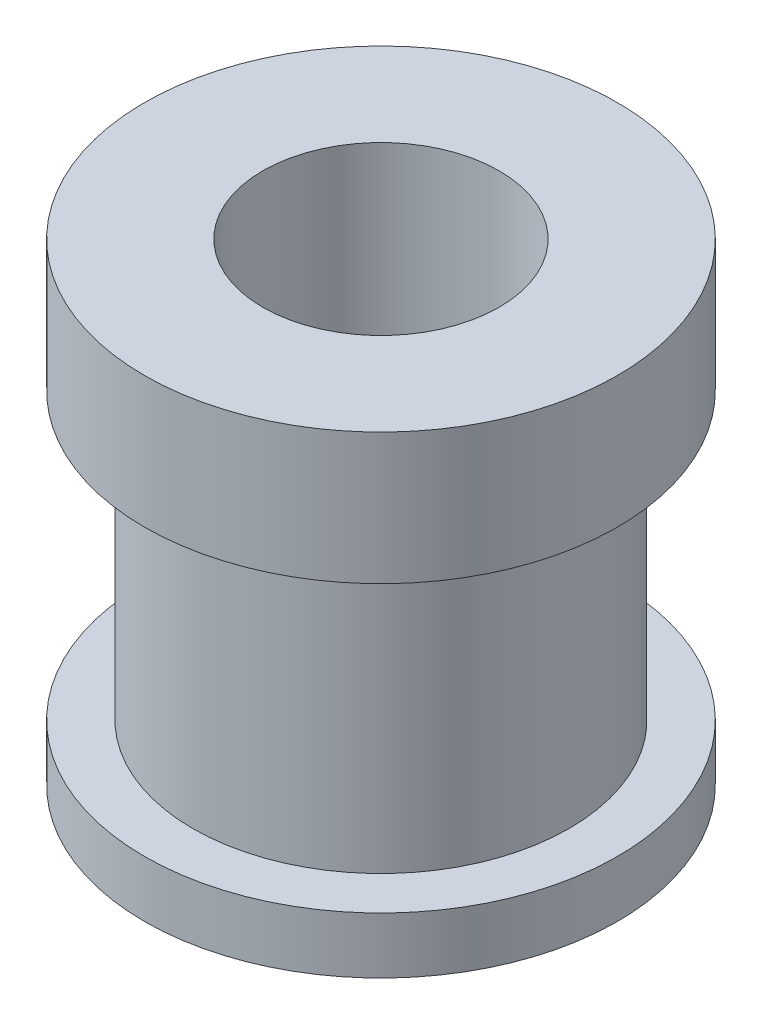
SolidWorks part; units mm, degrees
material "6063-T6"
ref_plane "Front Plane" through (0, 0, 0) normal (0, 0, 1) x (1, 0, 0)
ref_plane "Top Plane" through (0, 0, 0) normal (0, 1, 0) x (1, 0, 0)
ref_plane "Right Plane" through (0, 0, 0) normal (1, 0, 0) x (0, 0, -1)
sketch "Sketch1" plane through (0, 0, 0) normal (0, 1, 0) x (1, 0, 0)
  circle A0 centre (0, 0) radius 8
  dimension "D1" = 16
extrude "Boss-Extrude1" add sketch "Sketch1" along normal blind 8 and the other way blind 8
sketch "Sketch2" plane through (0, 0, 0) normal (0, 1, 0) x (1, 0, 0)
  circle A0 centre (0, 0) radius 6.365
  circle A1 centre (0, 0) radius 8
  dimension "D1" = 12.73
extrude "Cut-Extrude1" cut sketch "Sketch2" against normal blind 6.094 and the other way blind 3.556
sketch "Sketch3" plane through (0, 8, 0) normal (0, 1, 0) x (1, 0, 0)
  circle A0 centre (0, 0) radius 4
  dimension "D1" = 8
extrude "Cut-Extrude2" cut sketch "Sketch3" against normal through all
equation "\"pulley_pitch_diam\"= 12.73mm"
equation "\"D1@Sketch2\"=\"pulley_pitch_diam\""
equation "\"pulley_total_width\"= 16mm"
equation "\"belt_width\"= 6mm"
